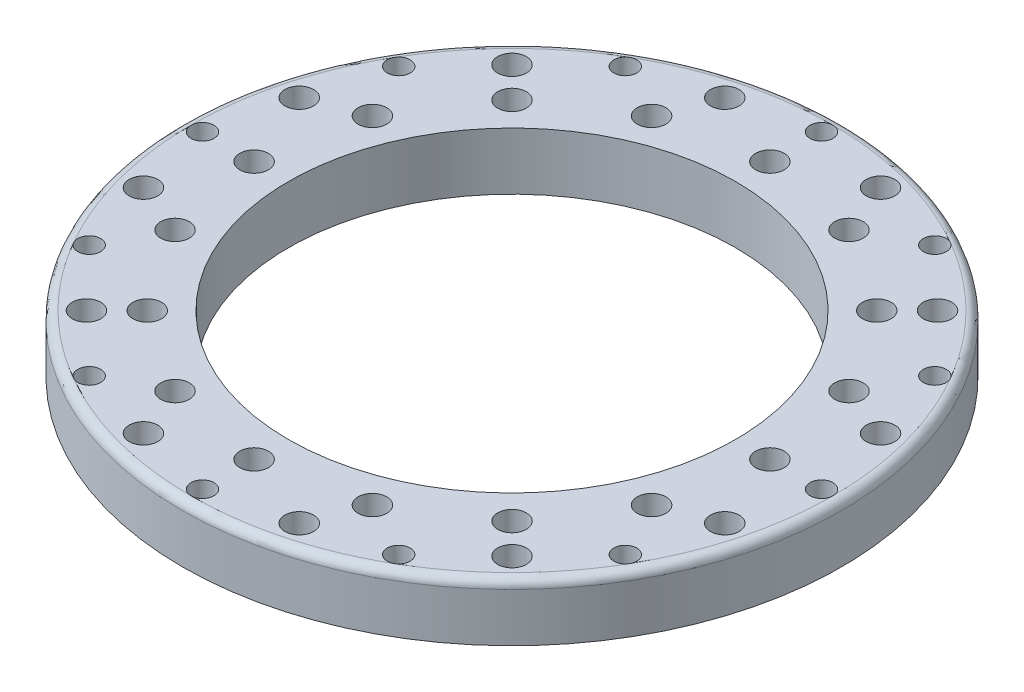
SolidWorks part; units mm, degrees
ref_plane "Front Plane" through (0, 0, 0) normal (0, 0, 1) x (1, 0, 0)
ref_plane "Top Plane" through (0, 0, 0) normal (0, 1, 0) x (1, 0, 0)
ref_plane "Right Plane" through (0, 0, 0) normal (1, 0, 0) x (0, 0, -1)
sketch "Sketch1" plane through (0, 0, 0) normal (0, 1, 0) x (1, 0, 0)
  line L0 (0, 0) -> (0, 52.5) construction
  line L1 (0, 0) -> (13.588, 50.7111) construction
  circle A12 centre (0, 0) radius 39
  circle A13 centre (0, 0) radius 57.5
  circle A14 centre (0, 0) radius 54 construction
  circle A15 centre (0, 54) radius 2
  circle A16 centre (27, 46.7654) radius 2
  circle A17 centre (46.7654, 27) radius 2
  circle A18 centre (54, 0) radius 2
  circle A19 centre (46.7654, -27) radius 2
  circle A20 centre (27, -46.7654) radius 2
  circle A21 centre (0, -54) radius 2
  circle A22 centre (-27, -46.7654) radius 2
  circle A23 centre (-46.7654, -27) radius 2
  circle A24 centre (-54, 0) radius 2
  circle A25 centre (-46.7654, 27) radius 2
  circle A26 centre (-27, 46.7654) radius 2
  circle A27 centre (0, 0) radius 52.5 construction
  circle A34 centre (13.588, 50.7111) radius 2.5
  circle A35 centre (37.1231, 37.1231) radius 2.5
  circle A36 centre (50.7111, 13.588) radius 2.5
  circle A37 centre (50.7111, -13.588) radius 2.5
  circle A38 centre (37.1231, -37.1231) radius 2.5
  circle A39 centre (13.588, -50.7111) radius 2.5
  circle A40 centre (-13.588, -50.7111) radius 2.5
  circle A41 centre (-37.1231, -37.1231) radius 2.5
  circle A42 centre (-50.7111, -13.588) radius 2.5
  circle A43 centre (-50.7111, 13.588) radius 2.5
  circle A44 centre (-37.1231, 37.1231) radius 2.5
  circle A45 centre (-13.588, 50.7111) radius 2.5
  point P21 (0, 0)
  point P28 (0, 0)
  point P56 (0, 0)
  point P60 (0, 0)
  dimension "D1" = 105
  dimension "D2" = 15
  dimension "D4" = 115
  dimension "D5" = 78
  dimension "D6" = 108
  dimension "D7" = 4
  dimension "D3" = 5
  dimension "D8" = 12
extrude "Boss-Extrude1" add sketch "Sketch1" along normal blind 10
sketch "Sketch2" plane through (0, 10, 0) normal (0, 1, 0) x (1, 0, 0)
  circle A0 centre (0, 0) radius 45 construction
  circle A1 centre (0, 45) radius 2.5
  circle A2 centre (17.2208, 41.5746) radius 2.5
  circle A3 centre (31.8198, 31.8198) radius 2.5
  circle A4 centre (41.5746, 17.2208) radius 2.5
  circle A5 centre (45, 0) radius 2.5
  circle A6 centre (41.5746, -17.2208) radius 2.5
  circle A7 centre (31.8198, -31.8198) radius 2.5
  circle A8 centre (17.2208, -41.5746) radius 2.5
  circle A9 centre (0, -45) radius 2.5
  circle A10 centre (-17.2208, -41.5746) radius 2.5
  circle A11 centre (-31.8198, -31.8198) radius 2.5
  circle A12 centre (-41.5746, -17.2208) radius 2.5
  circle A13 centre (-45, 0) radius 2.5
  circle A14 centre (-41.5746, 17.2208) radius 2.5
  circle A15 centre (-31.8198, 31.8198) radius 2.5
  circle A16 centre (-17.2208, 41.5746) radius 2.5
  point P27 (0, 0)
  dimension "D1" = 90
  dimension "D2" = 5
  dimension "D3" = 16
extrude "Cut-Extrude1" cut sketch "Sketch2" against normal blind 10
sketch "Sketch4" plane through (0, 0, 0) normal (0, 1, 0) x (1, 0, 0)
  circle A0 centre (0, 0) radius 45 construction
  circle A1 centre (0, 45) radius 5
  circle A2 centre (0, 45) radius 2.5
  circle A3 centre (17.2208, 41.5746) radius 2.5
  circle A4 centre (31.8198, 31.8198) radius 2.5
  circle A5 centre (41.5746, 17.2208) radius 2.5
  circle A6 centre (45, 0) radius 2.5
  circle A7 centre (41.5746, -17.2208) radius 2.5
  circle A8 centre (31.8198, -31.8198) radius 2.5
  circle A9 centre (17.2208, -41.5746) radius 2.5
  circle A10 centre (0, -45) radius 2.5
  circle A11 centre (-17.2208, -41.5746) radius 2.5
  circle A12 centre (-31.8198, -31.8198) radius 2.5
  circle A13 centre (17.2208, 41.5746) radius 5
  circle A14 centre (31.8198, 31.8198) radius 5
  circle A15 centre (41.5746, 17.2208) radius 5
  circle A16 centre (45, 0) radius 5
  circle A17 centre (41.5746, -17.2208) radius 5
  circle A18 centre (31.8198, -31.8198) radius 5
  circle A19 centre (17.2208, -41.5746) radius 5
  circle A20 centre (0, -45) radius 5
  circle A21 centre (-17.2208, -41.5746) radius 5
  circle A22 centre (-31.8198, -31.8198) radius 5
  circle A23 centre (-41.5746, -17.2208) radius 5
  circle A24 centre (-45, 0) radius 5
  circle A25 centre (-41.5746, 17.2208) radius 5
  circle A26 centre (-31.8198, 31.8198) radius 5
  circle A27 centre (-17.2208, 41.5746) radius 5
  circle A28 centre (-41.5746, -17.2208) radius 2.5
  circle A29 centre (-45, 0) radius 2.5
  circle A30 centre (-41.5746, 17.2208) radius 2.5
  circle A31 centre (-31.8198, 31.8198) radius 2.5
  circle A32 centre (-17.2208, 41.5746) radius 2.5
  point P29 (0, 0)
  point P50 (0, 0)
  dimension "D1" = 10
  dimension "D2" = 16
  dimension "D3" = 16
extrude "Boss-Extrude3" add sketch "Sketch4" against normal blind 0.4
fillet "Fillet1" radius 1.5 1 edges at (0, 10, 57.5)
